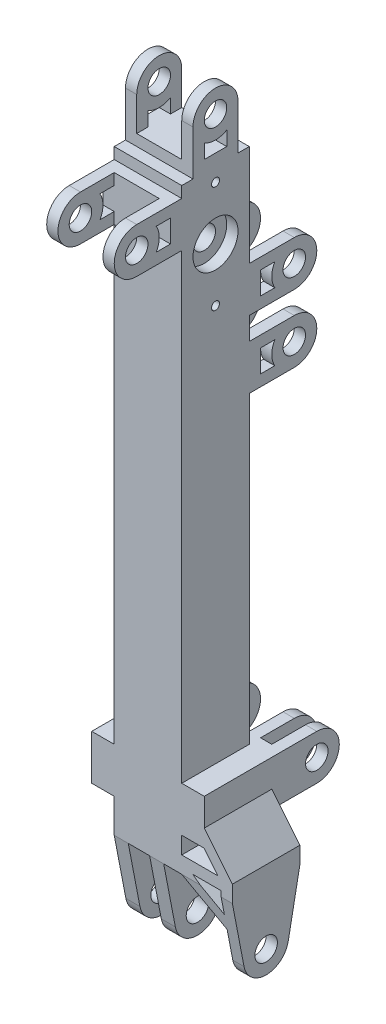
SolidWorks part; units mm, degrees
ref_plane "Front Plane" through (0, 0, 0) normal (0, 0, 1) x (1, 0, 0)
ref_plane "Top Plane" through (0, 0, 0) normal (0, 1, 0) x (1, 0, 0)
ref_plane "Right Plane" through (0, 0, 0) normal (1, 0, 0) x (0, 0, -1)
sketch "Sketch1" plane through (0, 0, 0) normal (0, 1, 0) x (1, 0, 0)
  line L1 (-9.525, -9.525) -> (9.525, -9.525)
  line L2 (-9.525, -9.525) -> (-9.525, 9.525)
  line L3 (-9.525, 9.525) -> (9.525, 9.525)
  line L4 (9.525, -9.525) -> (9.525, 9.525)
  line L5 (-9.525, -9.525) -> (9.525, 9.525) construction
  line L6 (-9.525, 9.525) -> (9.525, -9.525) construction
  point P0 (0, 0)
  dimension "D1" = 19.05
extrude "Boss-Extrude1" add sketch "Sketch1" along normal blind 190.5
sketch "Sketch2" plane through (0, 0, 0) normal (0, 1, 0) x (1, 0, 0)
  line L1 (-6.35, -6.35) -> (6.35, -6.35)
  line L2 (-6.35, -6.35) -> (-6.35, 6.35)
  line L3 (-6.35, 6.35) -> (6.35, 6.35)
  line L4 (6.35, -6.35) -> (6.35, 6.35)
  line L5 (-6.35, -6.35) -> (6.35, 6.35) construction
  line L6 (-6.35, 6.35) -> (6.35, -6.35) construction
  point P0 (0, 0)
  dimension "D1" = 12.7
extrude "Cut-Extrude1" cut sketch "Sketch2" along normal blind 120.65 from offset 25.4 contours L3 L4 L1 L2
sketch "Sketch4" plane through (0, 0, 0) normal (1, 0, 0) x (0, 0, -1)
  line L0 (-9.525, 190.5) -> (9.525, 190.5) construction
  circle A0 centre (0, 171.45) radius 6.35
  dimension "D1" = 12.7
  dimension "D2" = 19.05
extrude "Cut-Extrude2" cut sketch "Sketch4" against normal blind 3.175 from surface contours A0 starting at face at (9.525, 95.25, 0)
extrude "Cut-Extrude3" cut sketch "Sketch4<3>" along normal blind 3.175 from surface starting at face at (-9.525, 95.25, 0)
sketch "Sketch4<3>" plane through (0, 0, 0) normal (1, 0, 0) x (0, 0, -1) same geometry as "Sketch4"
sketch "Sketch5" plane through (0, 0, 0) normal (1, 0, 0) x (0, 0, -1)
  circle A0 centre (0, 171.45) radius 3.175
  dimension "D1" = 6.35
extrude "Cut-Extrude4" cut sketch "Sketch5" against normal through all both and the other way through all contours A0
hole_wizard "#4-40 Tapped Hole1" positions "Sketch6" profile "Sketch7" tap size "#4-40" standard "ANSI Inch" end condition through all
sketch "Sketch6" plane through (9.525, 0, 0) normal (1, 0, 0) x (0, 0, -1)
  line L0 (0, 186.5312) -> (0, 156.3688) construction
  circle A0 centre (0, 171.45) radius 3.175 construction
  point P0 (0, 186.5312)
  point P2 (0, 156.3688)
  point P9 (0, 171.45)
  dimension "D1" = 30.1625
sketch "Sketch7" plane through (9.525, 186.5312, 0) normal (0, 1, 0) x (0, 0, -1)
  line L0 (0, 0) -> (0, 19.05)
  line L1 (0, 19.05) -> (1.1303, 19.05)
  line L2 (1.1303, 19.05) -> (1.1303, 0)
  line L5 (1.1303, 0) -> (0, 0)
  line L11 (0, -6.35) -> (0, 107.95) construction
  dimension "Thru Tap Drill Dia." = 2.2606
  dimension "Thru Tap Drill Depth" = 19.05
cosmetic thread "Hole Thread1" parameters "D2"=2.8448
cosmetic thread "Hole Thread2" parameters "D2"=2.8448
sketch "Sketch8" plane through (0, 0, 0) normal (1, 0, 0) x (0, 0, -1)
  line L0 (-9.525, 25.4) -> (9.525, 25.4) construction
  line L1 (-9.525, 190.5) -> (-9.525, 0) construction
  line L2 (9.525, 190.5) -> (9.525, 0) construction
  line L4 (9.525, 22.225) -> (6.2354, 5.1488)
  line L5 (-6.2354, 5.1488) -> (-9.525, 22.225)
  line L7 (-9.525, 0) -> (9.525, 0) construction
  line L8 (-9.525, 22.225) -> (-9.525, 0)
  line L9 (-9.525, 0) -> (0, 0)
  line L10 (0, 0) -> (9.525, 0)
  line L11 (9.525, 0) -> (9.525, 22.225)
  arc A0 (6.2354, 5.1488) -> (-6.2354, 5.1488) centre (0, 6.35) cw
  circle A1 centre (0, 6.35) radius 3.175
  dimension "D3" = 6.35
  dimension "D4" = 6.35
  dimension "D1" = 3.175
  dimension "D2" = 19.05
extrude "Cut-Extrude5" cut sketch "Sketch8" against normal through all both and the other way through all contours L9 A0 L5 L8 | L4 A0 L10 L11 | A1 region at (0, 6.7606, -7.7085) region at (0, 6.7606, 7.7085) region at (0, 6.35, 0)
sketch "Sketch9" plane through (0, 0, 0) normal (0, 0, 1) x (1, 0, 0)
  line L0 (-9.525, 22.225) -> (9.525, 22.225) construction
  line L12 (0, 0) -> (0, 42.162) construction
  line L13 (-5.5562, 22.225) -> (-5.5563, 0)
  line L14 (0.4673, 0) -> (-5.5563, 0)
  line L15 (0.4673, 22.225) -> (0.4673, 0)
  line L16 (0.4673, 22.225) -> (-5.5562, 22.225)
  line L17 (4.4361, 22.225) -> (4.4361, 0)
  line L18 (9.525, 0) -> (4.4361, 0)
  line L19 (9.525, 22.225) -> (9.525, 0)
  line L20 (9.525, 22.225) -> (4.4361, 22.225)
  line L21 (9.525, 5.1488) -> (9.525, 22.225) construction
  line L22 (-9.525, 0) -> (9.525, 0) construction
  line L24 (-9.525, 5.1488) -> (-9.525, 22.225) construction
  dimension "D2" = 3.9688
  dimension "D3" = 6.0236
  dimension "D4" = 3.9687
extrude "Cut-Extrude6" cut sketch "Sketch9" against normal through all both and the other way through all
hole_wizard "#4-40 Tapped Hole2" positions "Sketch10" profile "Sketch11" tap size "#4-40" standard "ANSI Inch" end condition up to next
sketch "Sketch10" plane through (-9.525, 0, 0) normal (-1, 0, 0) x (0, 0, 1)
  point P0 (0, 20.6375)
  point P2 (0, 14.2875)
  dimension "D1" = 1.5875
  dimension "D2" = 6.35
sketch "Sketch11" plane through (-9.525, 20.6375, 0) normal (0, 1, 0) x (0, 0, 1)
  line L0 (0, 0) -> (0, 3.9688)
  line L1 (0, 3.9688) -> (1.1303, 3.9688)
  line L2 (1.1303, 3.9688) -> (1.1303, 0)
  line L5 (1.1303, 0) -> (0, 0)
  line L11 (0, -6.35) -> (0, 107.95) construction
  dimension "Thru Tap Drill Dia." = 2.2606
  dimension "Thru Tap Drill Depth" = 3.9688
cosmetic thread "Hole Thread3" parameters "D2"=2.8448
cosmetic thread "Hole Thread4" parameters "D2"=2.8448
sketch "Sketch12" plane through (0, 0, 0) normal (1, 0, 0) x (0, 0, -1)
  line L0 (-9.525, 187.325) -> (-9.525, 174.625)
  line L1 (-9.525, 190.5) -> (-9.525, 22.225) construction
  line L2 (-9.525, 174.625) -> (-22.225, 174.625)
  line L3 (-9.525, 187.325) -> (-22.225, 187.325)
  line L4 (-12.7, 184.15) -> (-12.7, 177.8)
  line L5 (-12.7, 177.8) -> (-16.7257, 177.8)
  line L6 (-12.7, 184.15) -> (-16.7257, 184.15)
  line L7 (-14.7129, 184.15) -> (-14.7129, 187.325) construction
  line L8 (-14.7129, 177.8) -> (-14.7129, 174.625) construction
  line L9 (-12.7, 180.975) -> (-9.525, 180.975) construction
  line L10 (-9.525, 190.5) -> (9.525, 190.5) construction
  arc A0 (-22.225, 187.325) -> (-22.225, 174.625) centre (-22.225, 180.975) ccw
  circle A1 centre (-22.225, 180.975) radius 3.175
  arc A2 (-16.7257, 184.15) -> (-16.7257, 177.8) centre (-22.225, 180.975) cw
  point P18 (-12.7, 181.7848)
  dimension "D2" = 6.35
  dimension "D3" = 12.7
  dimension "D1" = 12.7
  dimension "D4" = 3.175
  dimension "D5" = 9.525
extrude "Boss-Extrude2" add sketch "Sketch12" along normal up to surface and the other way up to surface up to face at (9.525, 106.3625, 0) other way up to face at (-9.525, 71.7665, 0)
sketch "Sketch13" plane through (0, 187.325, 0) normal (0, 1, 0) x (1, 0, 0)
  line L0 (-9.525, -28.575) -> (9.525, -28.575) construction
  line L1 (-6.35, -12.7) -> (6.35, -12.7)
  line L2 (-6.35, -12.7) -> (-6.35, -28.575)
  line L3 (-6.35, -28.575) -> (6.35, -28.575)
  line L4 (6.35, -12.7) -> (6.35, -28.575)
  line L5 (0, -12.7) -> (0, 0) construction
  line L6 (9.525, -22.225) -> (9.525, -9.525) construction
  line L7 (9.525, -9.525) -> (-9.525, -9.525) construction
  dimension "D1" = 3.175
  dimension "D2" = 3.175
extrude "Cut-Extrude7" cut sketch "Sketch13" against normal up to next contours L2 L3 L4 L1
sketch "Sketch15" plane through (0, 0, 0) normal (1, 0, 0) x (0, 0, -1)
  line L11 (-6.35, 190.5) -> (6.35, 190.5)
  line L12 (-9.525, 190.5) -> (9.525, 190.5) construction
  line L13 (6.35, 190.5) -> (6.35, 203.2)
  line L14 (-6.35, 203.2) -> (-6.35, 190.5)
  line L15 (-3.175, 193.675) -> (3.175, 193.675)
  line L16 (3.175, 193.675) -> (3.175, 197.7007)
  line L17 (-3.175, 193.675) -> (-3.175, 197.7007)
  line L18 (0, 190.5) -> (0, 193.675) construction
  line L19 (3.175, 195.6879) -> (6.35, 195.6879) construction
  line L20 (-3.175, 195.6879) -> (-6.35, 195.6879) construction
  arc A3 (6.35, 203.2) -> (-6.35, 203.2) centre (0, 203.2) ccw
  circle A4 centre (0, 203.2) radius 3.175
  arc A5 (-3.175, 197.7007) -> (3.175, 197.7007) centre (0, 203.2) ccw
  point P34 (3.3264, 195.6879)
  point P35 (0.0248, 203.2)
  dimension "D8" = 6.35
  dimension "D5" = 12.7
  dimension "D6" = 12.7
  dimension "D7" = 3.175
extrude "Boss-Extrude3" add sketch "Sketch15" along normal up to surface and the other way up to surface up to face at (9.525, 143.6687, 8.7313) other way up to face at (-9.525, 115.4499, 6.985)
sketch "Sketch16" plane through (0, 0, -6.35) normal (0, 0, -1) x (-1, 0, 0)
  line L0 (9.525, 209.55) -> (-9.525, 209.55) construction
  line L1 (-6.35, 209.55) -> (6.35, 209.55)
  line L2 (-6.35, 209.55) -> (-6.35, 193.675)
  line L3 (-6.35, 193.675) -> (6.35, 193.675)
  line L4 (6.35, 209.55) -> (6.35, 193.675)
  line L5 (-9.525, 190.5) -> (9.525, 190.5) construction
  line L7 (0, 193.675) -> (0, 190.5) construction
  line L8 (-9.525, 190.5) -> (9.525, 190.5) construction
  line L9 (6.35, 201.6125) -> (9.525, 201.6125) construction
  line L10 (9.525, 203.2) -> (9.525, 190.5) construction
  line L11 (-6.35, 201.6125) -> (-9.525, 201.6125) construction
  line L12 (-9.525, 203.2) -> (-9.525, 190.5) construction
  dimension "D1" = 3.175
extrude "Cut-Extrude8" cut sketch "Sketch16" against normal up to next
sketch "Sketch17" plane through (0, 0, 0) normal (1, 0, 0) x (0, 0, -1)
  line L1 (9.525, 161.925) -> (9.525, 149.225)
  line L7 (9.525, 190.5) -> (9.525, 22.225) construction
  line L8 (9.525, 149.225) -> (22.225, 149.225)
  line L9 (22.225, 161.925) -> (9.525, 161.925)
  line L10 (12.7, 158.75) -> (12.7, 152.4)
  line L12 (12.7, 152.4) -> (16.7257, 152.4)
  line L21 (12.7, 158.75) -> (16.7257, 158.75)
  line L22 (14.7129, 152.4) -> (14.7129, 149.225) construction
  line L23 (12.7, 155.575) -> (9.525, 155.575) construction
  line L24 (14.7129, 158.75) -> (14.7129, 161.925) construction
  line L25 (6.35, 190.5) -> (9.525, 190.5) construction
  arc A6 (22.225, 149.225) -> (22.225, 161.925) centre (22.225, 155.575) ccw
  circle A7 centre (22.225, 155.575) radius 3.175
  arc A8 (16.7257, 152.4) -> (16.7257, 158.75) centre (22.225, 155.575) cw
  point P34 (22.225, 153.5911)
  dimension "D2" = 6.35
  dimension "D3" = 12.7
  dimension "D1" = 12.7
  dimension "D4" = 3.175
  dimension "D9" = 34.925
extrude "Boss-Extrude4" add sketch "Sketch17" along normal up to surface and the other way up to surface up to face at (9.525, 161.925, 5.8208) other way up to face at (-9.525, 139.1606, 4.9893)
sketch "Sketch18" plane through (0, 161.925, 0) normal (0, 1, 0) x (1, 0, 0)
  line L0 (9.525, 28.575) -> (-9.525, 28.575) construction
  line L1 (-6.35, 28.575) -> (6.35, 28.575)
  line L2 (-6.35, 28.575) -> (-6.35, 12.7)
  line L3 (-6.35, 12.7) -> (6.35, 12.7)
  line L4 (6.35, 28.575) -> (6.35, 12.7)
  line L5 (0, 12.7) -> (0, 9.525) construction
  line L6 (9.525, 9.525) -> (-9.525, 9.525) construction
  line L7 (6.35, 20.6375) -> (9.525, 20.6375) construction
  line L8 (9.525, 9.525) -> (9.525, 22.225) construction
  line L9 (-6.35, 20.6375) -> (-9.525, 20.6375) construction
  dimension "D1" = 3.175
extrude "Cut-Extrude9" cut sketch "Sketch18" against normal up to next
sketch "Sketch19" plane through (0, 0, 0) normal (1, 0, 0) x (0, 0, -1)
  line L1 (9.525, 142.875) -> (9.525, 130.175)
  line L8 (9.525, 130.175) -> (22.225, 130.175)
  line L9 (22.225, 142.875) -> (9.525, 142.875)
  line L10 (12.7, 139.7) -> (12.7, 133.35)
  line L12 (12.7, 133.35) -> (16.7257, 133.35)
  line L18 (9.525, 149.225) -> (9.525, 22.225) construction
  line L19 (6.35, 190.5) -> (9.525, 190.5) construction
  line L21 (12.7, 139.7) -> (16.7257, 139.7)
  line L22 (14.7129, 133.35) -> (14.7129, 130.175) construction
  line L23 (12.7, 136.525) -> (9.525, 136.525) construction
  line L24 (14.7129, 139.7) -> (14.7129, 142.875) construction
  arc A6 (22.225, 130.175) -> (22.225, 142.875) centre (22.225, 136.525) ccw
  circle A7 centre (22.225, 136.525) radius 3.175
  arc A8 (16.7257, 133.35) -> (16.7257, 139.7) centre (22.225, 136.525) cw
  point P2 (27.6422, 129.7621)
  point P34 (22.225, 153.5911)
  dimension "D2" = 6.35
  dimension "D3" = 12.7
  dimension "D1" = 12.7
  dimension "D4" = 3.175
  dimension "D5" = 47.625
extrude "Boss-Extrude5" add sketch "Sketch19" along normal up to surface and the other way up to surface up to face at (9.525, 160.3375, 0) other way up to face at (-9.525, 142.8083, 0)
sketch "Sketch20" plane through (0, 142.875, 0) normal (0, 1, 0) x (1, 0, 0)
  line L1 (-6.35, 12.7) -> (6.35, 12.7)
  line L2 (-6.35, 12.7) -> (-6.35, 28.575)
  line L3 (-6.35, 28.575) -> (6.35, 28.575)
  line L4 (6.35, 12.7) -> (6.35, 28.575)
extrude "Cut-Extrude10" cut sketch "Sketch20" against normal up to next
ref_plane "Plane1" through (0, 38.1, 0) normal (0, -1, 0) x (-1, 0, 0)
sketch "Sketch24" plane through (0, 38.1, 0) normal (0, -1, 0) x (-1, 0, 0)
  line L0 (15.875, -9.525) -> (15.875, 28.575)
  line L1 (15.875, 28.575) -> (12.7, 28.575)
  line L2 (12.7, 28.575) -> (12.7, 12.7)
  line L3 (12.7, 12.7) -> (9.525, 12.7)
  line L4 (9.525, 12.7) -> (9.525, 28.575)
  line L5 (9.525, 28.575) -> (6.35, 28.575)
  line L6 (6.35, 28.575) -> (6.35, 12.7)
  line L7 (6.35, 12.7) -> (-6.35, 12.7)
  line L8 (-6.35, 12.7) -> (-6.35, 28.575)
  line L9 (-6.35, 28.575) -> (-9.525, 28.575)
  line L10 (-9.525, 28.575) -> (-9.525, 12.7)
  line L11 (-9.525, 12.7) -> (-12.7, 12.7)
  line L12 (-12.7, 12.7) -> (-12.7, 28.575)
  line L13 (-12.7, 28.575) -> (-15.875, 28.575)
  line L14 (-15.875, 28.575) -> (-15.875, -9.525)
  line L15 (-15.875, -9.525) -> (-9.525, -9.525)
  line L16 (-9.525, -9.525) -> (-9.525, 9.525)
  line L17 (-9.525, 9.525) -> (9.525, 9.525)
  line L18 (9.525, 9.525) -> (9.525, -9.525)
  line L19 (9.525, -9.525) -> (15.875, -9.525)
  line L20 (0, 12.7) -> (0, 9.525) construction
  line L21 (-9.525, 9.525) -> (9.525, 9.525) construction
  line L22 (9.525, 9.525) -> (9.525, 6.35) construction
  line L23 (-9.525, -9.525) -> (-4.4361, -9.525) construction
  point P22 (0, 0)
  point P23 (0, 0)
  point P24 (0, 0)
  point P25 (0, 0)
  point P26 (0, 0)
  point P27 (-17.0918, -5.6243)
  point P28 (13.7962, -4.1708)
  point P29 (10.98, 28.5341)
  point P30 (15.3406, 31.4412)
  point P31 (-8.5521, 15.4522)
  point P32 (0, 15.1796)
  point P34 (0, 15.9186)
  point P37 (0, 0)
  point P38 (-13.7133, -6.35)
  dimension "D1" = 12.7
  dimension "D2" = 3.175
  dimension "D4" = 19.05
extrude "Boss-Extrude6" add sketch "Sketch24" along normal mid plane 12.7 contours L14 L15 L16 L17 L18 L19 L0 L1 L2 L3 L4 L5 L6 L7 L8 L9 L10 L11 L12 L13
sketch "Sketch25" plane through (0, 0, 0) normal (1, 0, 0) x (0, 0, -1)
  line L0 (-39.3712, 38.1) -> (39.3712, 38.1) construction
  line L1 (28.575, 31.75) -> (28.575, 44.45) construction
  line L2 (28.575, 44.45) -> (-9.525, 44.45) construction
  line L3 (22.225, 44.45) -> (28.575, 44.45)
  line L4 (28.575, 44.45) -> (28.575, 38.1)
  line L5 (28.575, 38.1) -> (28.575, 31.75)
  line L6 (28.575, 31.75) -> (22.225, 31.75)
  arc A0 (22.225, 31.75) -> (22.225, 44.45) centre (22.225, 38.1) ccw
  circle A1 centre (22.225, 38.1) radius 3.175
  dimension "D1" = 6.35
extrude "Cut-Extrude11" cut sketch "Sketch25" against normal through all both and the other way through all contours A0 L4 L3 | A0 L6 L5 | A1 region at (0, 33.1684, -27.1566) region at (0, 43.0316, -27.1566)
sketch "Sketch23" plane through (0, 0, 0) normal (0, 0, 1) x (1, 0, 0)
  line L0 (12.7, 23.7656) -> (20.6375, 23.7656)
  line L1 (20.6375, 23.7656) -> (20.6375, 17.5122)
  line L2 (20.6375, 0) -> (23.8125, 0)
  line L3 (23.8125, 0) -> (23.8125, 26.9406)
  line L4 (19.7146, 26.9406) -> (9.525, 26.9406)
  line L5 (9.525, 174.625) -> (9.525, 44.45) construction
  line L6 (20.6375, 13.4703) -> (20.6375, 0)
  line L8 (9.525, 22.225) -> (9.525, 26.9406)
  line L9 (16.6687, 23.7656) -> (16.6687, 26.9406) construction
  line L10 (22.225, 0) -> (22.225, 12.7) construction
  line L11 (20.6375, 13.4703) -> (9.525, 22.225)
  line L12 (20.6375, 13.4703) -> (23.8125, 13.4703) construction
  line L13 (20.6375, 17.5122) -> (12.7, 23.7656)
  line L14 (16.6687, 20.6389) -> (14.7039, 18.1449) construction
  line L16 (19.7146, 26.9406) -> (15.7902, 31.75)
  line L17 (23.8125, 26.9406) -> (15.875, 36.668)
  line L21 (15.875, 31.75) -> (9.525, 31.75) construction
  line L22 (17.7524, 29.3453) -> (20.2124, 31.3526) construction
  line L23 (15.875, 36.668) -> (9.525, 44.45) construction
  line L24 (15.875, 31.75) -> (15.875, 44.45) construction
  line L25 (15.7902, 31.75) -> (15.875, 31.75)
  line L26 (15.875, 31.75) -> (15.875, 36.668)
  dimension "D1" = 14.2875
  dimension "D2" = 3.175
  dimension "D3" = 12.7
  dimension "D4" = 3.175
extrude "Boss-Extrude7" add sketch "Sketch23" along normal up to surface and the other way up to surface up to face at (-0.0435, 51.0117, 9.525) other way up to face at (-0.0933, 24.9464, -9.525)
sketch "Sketch28" plane through (23.8125, 0, 0) normal (1, 0, 0) x (0, 0, -1)
  line L0 (9.525, 22.225) -> (6.2354, 5.1488) construction
  line L1 (9.525, 13.4703) -> (9.525, 22.225) construction
  line L2 (9.525, 0) -> (9.525, 13.4703) construction
  line L3 (-9.525, 0) -> (9.525, 0) construction
  line L4 (-6.2354, 5.1488) -> (-9.525, 22.225) construction
  line L5 (-9.525, 13.4703) -> (-9.525, 22.225) construction
  line L6 (-9.525, 0) -> (-9.525, 13.4703) construction
  line L7 (9.525, 22.225) -> (6.2354, 5.1488)
  line L8 (9.525, 13.4703) -> (9.525, 22.225)
  line L9 (9.525, 0) -> (9.525, 13.4703)
  line L10 (-9.525, 0) -> (9.525, 0)
  line L11 (-6.2354, 5.1488) -> (-9.525, 22.225)
  line L12 (-9.525, 13.4703) -> (-9.525, 22.225)
  line L13 (-9.525, 0) -> (-9.525, 13.4703)
  arc A0 (-6.2354, 5.1488) -> (6.2354, 5.1488) centre (0, 6.35) ccw construction
  arc A1 (-6.2354, 5.1488) -> (6.2354, 5.1488) centre (0, 6.35) ccw
  circle A2 centre (0, 6.35) radius 3.175
  line M2 (-9.525, 26.9406) -> (-9.525, 0)
  line M3 (-9.525, 0) -> (9.525, 0)
  line M4 (9.525, 0) -> (9.525, 26.9406)
  dimension "D1" = 6.35
extrude "Cut-Extrude13" cut sketch "Sketch28" against normal up to next contours A1 L10 L7 M4 | A1 L11 M2 M3 | A2 region at (23.8125, 6.7606, -7.7085) region at (23.8125, 6.7606, 7.7085)
